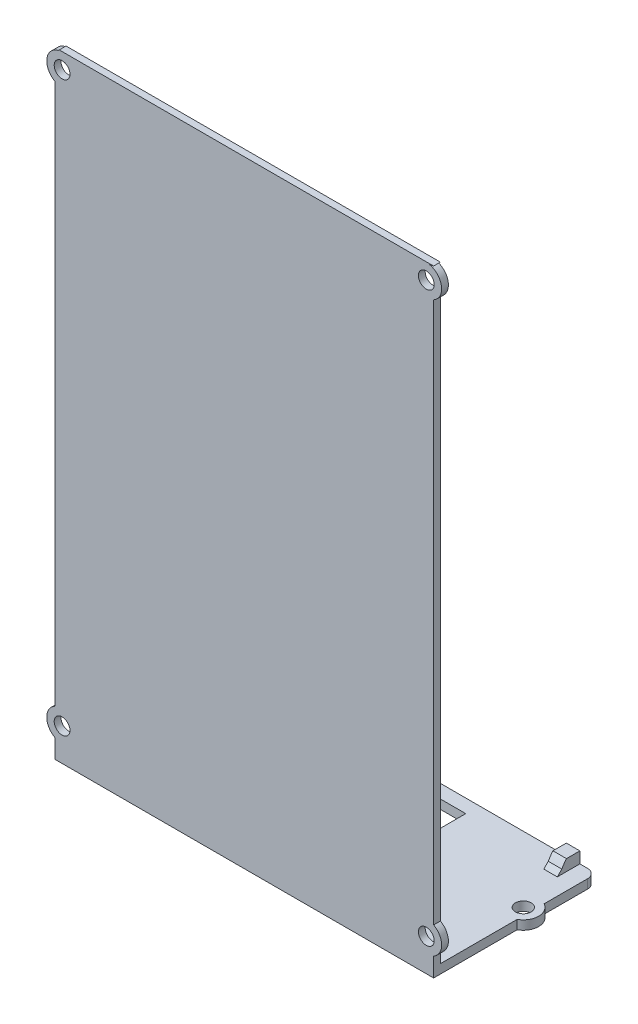
SolidWorks part; units mm, degrees
ref_plane "Front Plane" through (0, 0, 0) normal (0, 0, 1) x (1, 0, 0)
ref_plane "Top Plane" through (0, 0, 0) normal (0, 1, 0) x (1, 0, 0)
ref_plane "Right Plane" through (0, 0, 0) normal (1, 0, 0) x (0, 0, -1)
sketch "Sketch1" plane through (0, 0, 0) normal (0, 0, 1) x (1, 0, 0)
  line L0 (-38.75, -134.5) -> (38.75, -134.5)
  line L1 (-42, -126.5135) -> (-42, -6.4865) construction
  line L2 (-38.75, -132.4865) -> (-38.75, -134.5) construction
  line L3 (42, 0) -> (-42, 0) construction
  line L4 (42, -0.5135) -> (42, 0) construction
  line L5 (-38.75, -7) -> (-38.75, -126.5135) construction
  line L6 (38.75, -7) -> (-38.75, -7) construction
  line L28 (-42, -6.4865) -> (-42, -126.5135)
  line L29 (-42, -132.4865) -> (-42, -134.5)
  line L30 (-42, -134.5) -> (-38.75, -134.5)
  line L31 (-38.75, -134.5) -> (-38.1117, -132.0373) construction
  line L32 (-38.75, -126.5135) -> (-38.75, -7) construction
  line L33 (-38.75, -7) -> (38.75, -7) construction
  line L34 (38.75, -7) -> (38.75, -126.5135) construction
  line L35 (38.75, -132.4865) -> (38.75, -134.5) construction
  line L36 (38.75, -134.5) -> (42, -134.5)
  line L37 (42, -134.5) -> (42, -132.4865)
  line L38 (42, -126.5135) -> (42, -6.4865)
  line L39 (41.1041, -0.1791) -> (42, 0)
  line L40 (42, 0) -> (-41, 0)
  line L41 (-41, 0) -> (-41.193, -0.1999)
  circle A0 centre (-40.375, -129.5) radius 1.75
  circle A1 centre (40.375, -129.5) radius 1.75
  circle A2 centre (40.375, -3.5) radius 1.75
  circle A3 centre (-40.375, -3.5) radius 1.75
  arc A4 (-38.75, -132.4865) -> (-38.75, -126.5135) centre (-40.375, -129.5) ccw construction
  arc A5 (42, -6.4865) -> (42, -0.5135) centre (40.375, -3.5) ccw construction
  arc A12 (-42, -126.5135) -> (-42, -132.4865) centre (-40.375, -129.5) ccw
  arc A13 (-38.1117, -132.0373) -> (-38.75, -126.5135) centre (-40.375, -129.5) ccw construction
  arc A14 (38.75, -126.5135) -> (38.75, -132.4865) centre (40.375, -129.5) ccw construction
  arc A15 (42, -132.4865) -> (42, -126.5135) centre (40.375, -129.5) ccw
  arc A16 (42, -6.4865) -> (41.1041, -0.1791) centre (40.375, -3.5) ccw
  arc A17 (-41.193, -0.1999) -> (-42, -6.4865) centre (-40.375, -3.5) ccw
  dimension "D2" = 3.5
extrude "Boss-Extrude1" add sketch "Sketch1" along normal blind 1.5
sketch "Sketch2" plane through (-42, 0, 0) normal (-1, 0, 0) x (0, 0, 1)
  line L0 (1.5, -134.5) -> (1.5, -136.7)
  line L1 (1.5, -136.7) -> (-40, -136.7)
  line L2 (-40, -136.7) -> (-40, -134.7)
  line L3 (-40, -134.7) -> (0, -134.7)
  line L4 (0, -134.7) -> (0, -134.5)
  line L10 (0, -132.4865) -> (0, -134.5)
  line L11 (0, -134.5) -> (1.5, -134.5)
  line L12 (1.5, -134.5) -> (1.5, -132.4865)
  line L13 (1.5, -132.4865) -> (0, -132.4865)
  line L14 (0, -132.4865) -> (0, -134.5)
  line L16 (1.5, -134.5) -> (1.5, -132.4865)
  line L17 (1.5, -132.4865) -> (0, -132.4865)
  dimension "D1" = 2
  dimension "D2" = 0.2
  dimension "D4" = 40
  dimension "D3" = 0
extrude "Boss-Extrude2" add sketch "Sketch2" against normal up to surface (113.8724 mm away)
sketch "Sketch3" plane through (-15, 0, 0) normal (1, 0, 0) x (0, 0, -1)
  line L0 (0, -119.7) -> (15, -134.7)
  line L1 (0, -126.5135) -> (0, -6.4865) construction
  line L2 (40, -134.7) -> (0, -134.7) construction
  line L3 (15, -134.7) -> (0, -134.7)
  line L4 (0, -134.7) -> (0, -119.7)
  dimension "D1" = 15
extrude "Boss-Extrude3" add sketch "Sketch3" along normal blind 1.5 and the other way blind 1.5
sketch "Sketch4" plane through (0, -136.7, 0) normal (0, -1, 0) x (1, 0, 0)
  line L0 (-42, -17.0135) -> (-42, -22.9865)
  line L1 (42, -17.0135) -> (42, -22.9865)
  line L9 (-42, -40) -> (-42, 1.5) construction
  line L10 (42, 1.5) -> (42, -40) construction
  line L11 (42, -17.0135) -> (40.375, -20) construction
  line L12 (40.375, -20) -> (42, -22.9865) construction
  arc A2 (-42, -17.0135) -> (-42, -22.9865) centre (-40.375, -20) ccw
  arc A3 (42, -22.9865) -> (42, -17.0135) centre (40.375, -20) ccw
  arc A4 (-42, -17.0135) -> (-42, -22.9865) centre (-40.375, -20) ccw construction
  arc A5 (42, -22.9865) -> (42, -17.0135) centre (40.375, -20) ccw construction
extrude "Boss-Extrude4" add sketch "Sketch4" against normal blind 2
sketch "Sketch5" plane through (0, -136.7, 0) normal (0, -1, 0) x (1, 0, 0)
  arc A0 (42, -22.9865) -> (42, -17.0135) centre (40.375, -20) ccw construction
  circle A1 centre (40.375, -20) radius 1.75
  circle A6 centre (-40.375, -20) radius 1.75
  arc A7 (-42, -17.0135) -> (-42, -22.9865) centre (-40.375, -20) ccw construction
  dimension "D1" = 3.5
  dimension "D2" = 3.5
extrude "Cut-Extrude1" cut sketch "Sketch5" against normal blind 2
sketch "Sketch6" plane through (0, -136.7, 0) normal (0, -1, 0) x (1, 0, 0)
  line L0 (-56.2543, -34.6207) -> (65.3337, -34.6207)
extrude "Cut-Extrude2" cut sketch "Sketch6" against normal through all and the other way through all
sketch "Sketch7" plane through (0, -136.7, 0) normal (0, -1, 0) x (1, 0, 0)
  line L0 (-42, -34.6207) -> (42, -34.6207) construction
  line L1 (-38.3, -34.6207) -> (-35.3, -34.6207)
  line L2 (-38.3, -34.6207) -> (-38.3, -30.6207)
  line L3 (-38.3, -30.6207) -> (-35.3, -30.6207)
  line L4 (-35.3, -34.6207) -> (-35.3, -30.6207)
  line L5 (-42, -28.8036) -> (-38.3, -28.8036) construction
  line L6 (38.3, -34.6207) -> (35.3, -34.6207)
  line L7 (38.3, -34.6207) -> (38.3, -30.6207)
  line L8 (38.3, -30.6207) -> (35.3, -30.6207)
  line L9 (35.3, -34.6207) -> (35.3, -30.6207)
  line L10 (-42, -34.6207) -> (-42, -22.9865) construction
  line L11 (38.3, -30.6207) -> (42, -30.6207) construction
  line L12 (42, -22.9865) -> (42, -34.6207) construction
  dimension "D1" = 3.7
  dimension "D2" = 3
  dimension "D3" = 4
extrude "Boss-Extrude6" add sketch "Sketch7" against normal blind 2.5 from surface at -2 starting at face at (-40.375, -134.7, -21.75)
fillet "Fillet1" radius 2 2 edges at (-42, -135.7, -34.6207) (42, -135.7, -34.6207)
chamfer "Chamfer1" distance 1 angle 45 4 edges at (-36.8, -132.2, -30.6207) (36.8, -132.2, -30.6207) (-36.8, -134.7, -30.6207) (36.8, -134.7, -30.6207)
fillet "Fillet2" radius 8 2 edges at (-36.8, -133.2, -30.6207) (36.8, -133.2, -30.6207)
sketch "Sketch8" plane through (0, -136.7, 0) normal (0, -1, 0) x (1, 0, 0)
  line L0 (-42, -17.0135) -> (-42, 1.5) construction
  line L1 (-10, -2.5) -> (16, -2.5)
  line L2 (-10, -2.5) -> (-10, -31.6207)
  line L3 (-10, -31.6207) -> (16, -31.6207)
  line L4 (16, -2.5) -> (16, -31.6207)
  line L5 (42, 1.5) -> (-42, 1.5) construction
  line L6 (-40, -34.6207) -> (40, -34.6207) construction
  dimension "D1" = 32
  dimension "D2" = 58
  dimension "D3" = 4
  dimension "D4" = 3
extrude "Cut-Extrude3" cut sketch "Sketch8" against normal blind 22.4262
